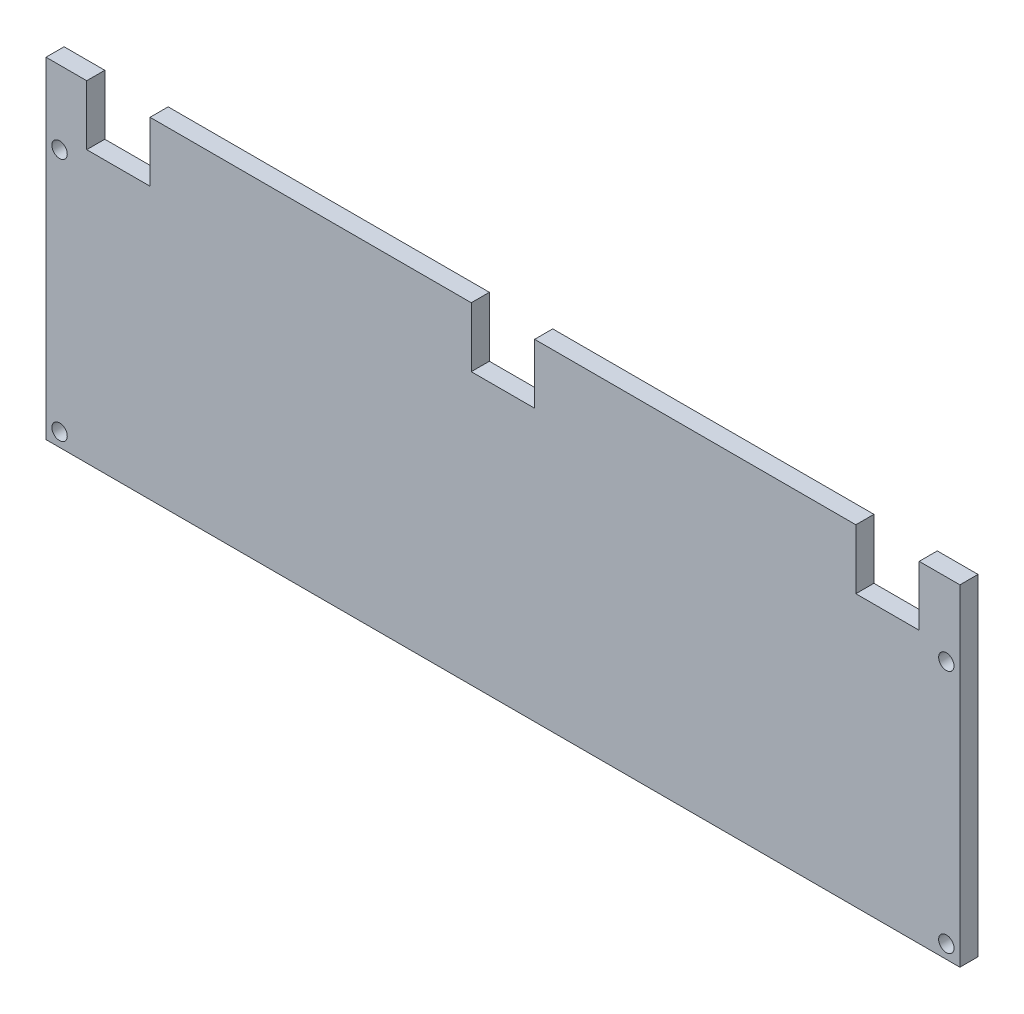
SolidWorks part; units mm, degrees
ref_plane "Ön Düzlem" through (0, 0, 0) normal (0, 0, 1) x (1, 0, 0)
ref_plane "Üst Düzlem" through (0, 0, 0) normal (0, 1, 0) x (1, 0, 0)
ref_plane "Sağ Düzlem" through (0, 0, 0) normal (1, 0, 0) x (0, 0, -1)
sketch "Çizim1" plane through (0, 0, 0) normal (0, 0, 1) x (1, 0, 0)
  line L1 (-252.5, -75) -> (252.5, -75)
  line L2 (-252.5, -75) -> (-252.5, 75)
  line L3 (-252.5, 75) -> (252.5, 75)
  line L4 (252.5, -75) -> (252.5, 75)
  line L5 (-252.5, -75) -> (252.5, 75) construction
  line L6 (-252.5, 75) -> (252.5, -75) construction
  point P0 (0, 0)
  dimension "D1" = 150
  dimension "D2" = 505
base flange "Taban-Flanş1" sketch "Çizim1" thickness 10 reverse thickness direction no parameters "D1"=0.7366
sketch "Çizim2" plane through (0, 0, 0) normal (0, 0, 1) x (1, 0, 0)
  line L0 (252.5, 75) -> (-252.5, 75) construction
  line L1 (-252.5, 75) -> (-252.5, -75) construction
  line L2 (0, -5.5) -> (0, 5.5) construction
  circle A0 centre (-245, 67.5) radius 4.25
  circle A1 centre (245, 67.5) radius 4.25
  dimension "D1" = 8.5
  dimension "D2" = 7.5
  dimension "D3" = 7.5
extrude "Kes-Ekstrüzyon1" cut sketch "Çizim2" against normal blind 10 normal cut yes
mirror "Aynalama1" about plane through (0, 0, 0) normal (0, 1, 0) of "Kes-Ekstrüzyon1"
sketch "Çizim3" plane through (0, 0, 0) normal (0, 0, 1) x (1, 0, 0)
  line L25 (252.5, 75) -> (230, 75)
  line L26 (252.5, 75) -> (252.5, 108)
  line L27 (252.5, 108) -> (230, 108)
  line L28 (230, 75) -> (230, 108)
  line L30 (195, 75) -> (17.5, 75)
  line L31 (195, 75) -> (195, 108)
  line L32 (195, 108) -> (17.5, 108)
  line L33 (17.5, 75) -> (17.5, 108)
  line L37 (-17.5, 75) -> (-195, 75)
  line L38 (-17.5, 75) -> (-17.5, 108)
  line L39 (-17.5, 108) -> (-195, 108)
  line L40 (-195, 75) -> (-195, 108)
  line L43 (-230, 75) -> (-252.5, 75)
  line L44 (-230, 75) -> (-230, 108)
  line L45 (-230, 108) -> (-252.5, 108)
  line L46 (-252.5, 75) -> (-252.5, 108)
  dimension "D1" = 33
  dimension "D2" = 35
  dimension "D3" = 35
  dimension "D4" = 35
  dimension "D5" = 22.5
  dimension "D6" = 177.5
  dimension "D7" = 177.5
  dimension "D8" = 22.5
base flange "Sekme1" sketch "Çizim3" thickness 10 reverse thickness direction no parameters "D1"=0.7366
sketch "Büküm-Çizgileri1" [suppressed] plane through (0, 0, 0) normal (0, 1, 0) x (1, 0, 0)
sketch "Sınırlandırma-Kutusu1" [suppressed] plane through (0, 0, 0) normal (0, 1, 0) x (1, 0, 0)
sheet metal parameters "Sac-Levha1" thickness 10 parameters "D1"=0.7366
flat pattern "Düz-Çoğaltma1" [suppressed]
sketch "Büküm-Çizgileri2" plane through (0, 0, 0) normal (0, 1, 0) x (1, 0, 0)
sketch3d "Sınırlandırma-Kutusu2" [suppressed]
  line L0 (252.5, -75, 0) -> (-252.5, -75, 0) construction
  line L1 (252.5, 75, 0) -> (-252.5, 75, 0) construction
  line L2 (252.5, -75, 0) -> (252.5, 75, 0) construction
  line L3 (-252.5, -75, 0) -> (-252.5, 75, 0) construction
sheet metal parameters "Sac-Levha2" thickness 10 parameters "D1"=0.7366
flat pattern "Düz-Çoğaltma1"
sketch "Büküm-Çizgileri2" plane through (0, 0, 0) normal (0, 1, 0) x (1, 0, 0)
sketch3d "Sınırlandırma-Kutusu2" [suppressed]
  line L0 (-252.5, -75, 0) -> (252.5, -75, 0) construction
  line L1 (-252.5, 75, 0) -> (252.5, 75, 0) construction
  line L2 (-252.5, -75, 0) -> (-252.5, 75, 0) construction
  line L3 (252.5, -75, 0) -> (252.5, 75, 0) construction
sheet metal parameters "Sac-Levha3" thickness 10 parameters "D1"=0.7366
flat pattern "Düz-Çoğaltma1"
sketch "Büküm-Çizgileri2" plane through (0, 0, 0) normal (0, 1, 0) x (1, 0, 0)
sketch3d "Sınırlandırma-Kutusu2" [suppressed]
  line L0 (-252.5, -75, 0) -> (252.5, -75, 0) construction
  line L1 (-252.5, 75, 0) -> (252.5, 75, 0) construction
  line L2 (-252.5, -75, 0) -> (-252.5, 75, 0) construction
  line L3 (252.5, -75, 0) -> (252.5, 75, 0) construction
sheet metal parameters "Sac-Levha4" thickness 10 parameters "D1"=0.7366
flat pattern "Düz-Çoğaltma4"
sketch "Büküm-Çizgileri3" plane through (0, 0, 0) normal (0, 1, 0) x (1, 0, 0)
sketch3d "Sınırlandırma-Kutusu3" [suppressed]
  line L0 (-252.5, -75, 0) -> (252.5, -75, 0) construction
  line L1 (-252.5, 108, 0) -> (252.5, 108, 0) construction
  line L2 (-252.5, -75, 0) -> (-252.5, 108, 0) construction
  line L3 (252.5, -75, 0) -> (252.5, 108, 0) construction
